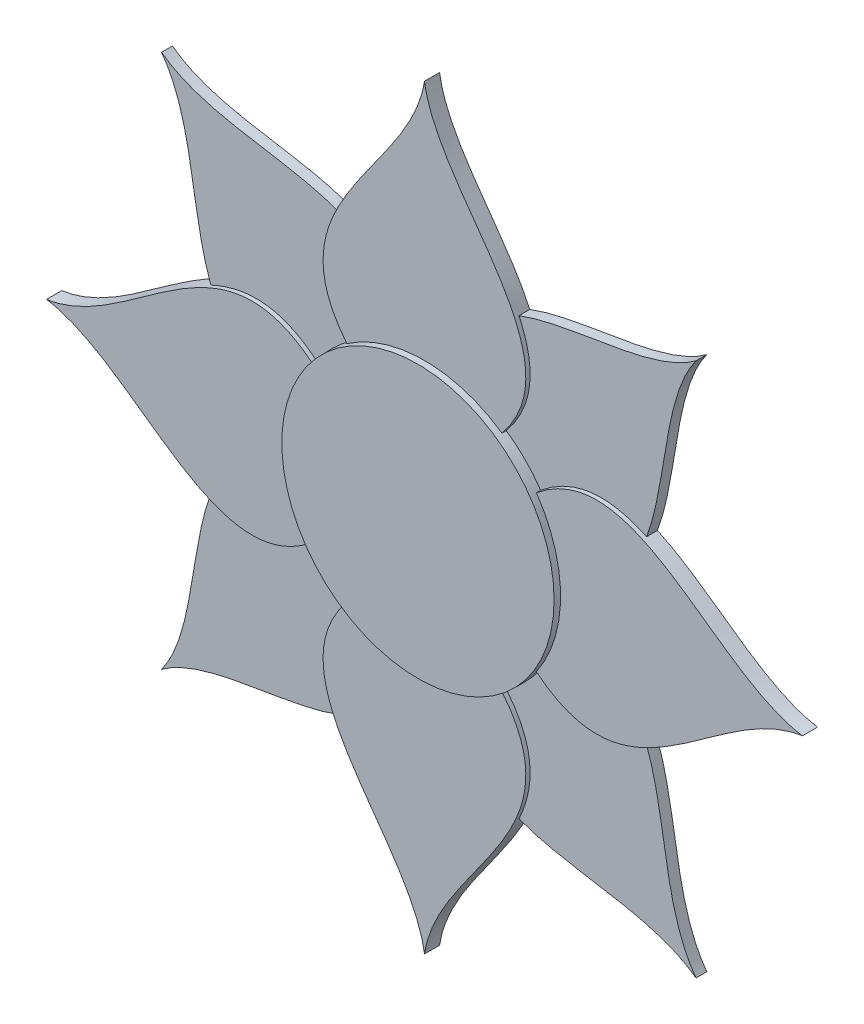
SolidWorks part; units mm, degrees
ref_plane "Front Plane" through (0, 0, 0) normal (0, 0, 1) x (1, 0, 0)
ref_plane "Top Plane" through (0, 0, 0) normal (0, 1, 0) x (1, 0, 0)
ref_plane "Right Plane" through (0, 0, 0) normal (1, 0, 0) x (0, 0, -1)
sketch "Sketch1" plane through (0, 0, 0) normal (0, 0, 1) x (1, 0, 0)
  circle A1 centre (0, 0) radius 63.0014
  spline S0 degree 3 poles (-35.8727, 51.7912) (-72.6487, 96.7225) (-6.1664, 133.6253) (0, 174.8878) knots 0 0 0 0 1 1 1 1
  spline S1 degree 3 poles (35.8727, 51.7912) (72.6487, 96.7225) (6.1664, 133.6253) (0, 174.8878) knots 0 0 0 0 1 1 1 1
  spline S2 degree 3 poles (100.8291, 41.7648) (110.4368, 67.4533) (108.4032, 103.0404) (123.6644, 123.6644) knots 0.385044 0.385044 0.385044 0.385044 1 1 1 1
  spline S3 degree 3 poles (41.7648, 100.8291) (67.4533, 110.4368) (103.0404, 108.4032) (123.6644, 123.6644) knots 0.385044 0.385044 0.385044 0.385044 1 1 1 1
  spline S4 degree 3 poles (51.7912, -35.8727) (96.7225, -72.6487) (133.6253, -6.1664) (174.8878, 0) knots 0 0 0 0 1 1 1 1
  spline S5 degree 3 poles (51.7912, 35.8727) (96.7225, 72.6487) (133.6253, 6.1664) (174.8878, 0) knots 0 0 0 0 1 1 1 1
  spline S6 degree 3 poles (41.7648, -100.8291) (67.4533, -110.4368) (103.0404, -108.4032) (123.6644, -123.6644) knots 0.385044 0.385044 0.385044 0.385044 1 1 1 1
  spline S7 degree 3 poles (100.8291, -41.7648) (110.4368, -67.4533) (108.4032, -103.0404) (123.6644, -123.6644) knots 0.385044 0.385044 0.385044 0.385044 1 1 1 1
  spline S8 degree 3 poles (-35.8727, -51.7912) (-72.6487, -96.7225) (-6.1664, -133.6253) (0, -174.8878) knots 0 0 0 0 1 1 1 1
  spline S9 degree 3 poles (35.8727, -51.7912) (72.6487, -96.7225) (6.1664, -133.6253) (0, -174.8878) knots 0 0 0 0 1 1 1 1
  spline S10 degree 3 poles (-100.8291, -41.7648) (-110.4368, -67.4533) (-108.4032, -103.0404) (-123.6644, -123.6644) knots 0.385044 0.385044 0.385044 0.385044 1 1 1 1
  spline S11 degree 3 poles (-41.7648, -100.8291) (-67.4533, -110.4368) (-103.0404, -108.4032) (-123.6644, -123.6644) knots 0.385044 0.385044 0.385044 0.385044 1 1 1 1
  spline S12 degree 3 poles (-51.7912, 35.8727) (-96.7225, 72.6487) (-133.6253, 6.1664) (-174.8878, 0) knots 0 0 0 0 1 1 1 1
  spline S13 degree 3 poles (-51.7912, -35.8727) (-96.7225, -72.6487) (-133.6253, -6.1664) (-174.8878, 0) knots 0 0 0 0 1 1 1 1
  spline S14 degree 3 poles (-41.7648, 100.8291) (-67.4533, 110.4368) (-103.0404, 108.4032) (-123.6644, 123.6644) knots 0.385044 0.385044 0.385044 0.385044 1 1 1 1
  spline S15 degree 3 poles (-100.8291, 41.7648) (-110.4368, 67.4533) (-108.4032, 103.0404) (-123.6644, 123.6644) knots 0.385044 0.385044 0.385044 0.385044 1 1 1 1
  point P13 (0, 0)
  point P71 (0, 0)
extrude "Boss-Extrude1" add sketch "Sketch1" along normal blind 10 contours A1 region at (0, 0, 0)
extrude "Boss-Extrude2" add sketch "Sketch1<3>" along normal blind 7 contours S13 A1 S12 | A1 S1 S0 | S5 A1 S4 | S9 A1 S8 region at (98.1678, 0, 0) region at (0, 98.1678, 0) region at (0, -98.1678, 0) region at (-98.1678, 0, 0)
sketch "Sketch1<3>" plane through (0, 0, 0) normal (0, 0, 1) x (1, 0, 0) same geometry as "Sketch1"
extrude "Boss-Extrude3" add sketch "Sketch1<4>" along normal blind 5 contours S15 S12 A1 S0 S14 | A1 S5 S2 S3 S1 | A1 S9 S6 S7 S4 | A1 S13 S10 S11 S8 region at (77.7269, 77.7269, 0) region at (77.7269, -77.7269, 0) region at (-77.7269, 77.7269, 0) region at (-77.7269, -77.7269, 0)
sketch "Sketch1<4>" plane through (0, 0, 0) normal (0, 0, 1) x (1, 0, 0) same geometry as "Sketch1"
